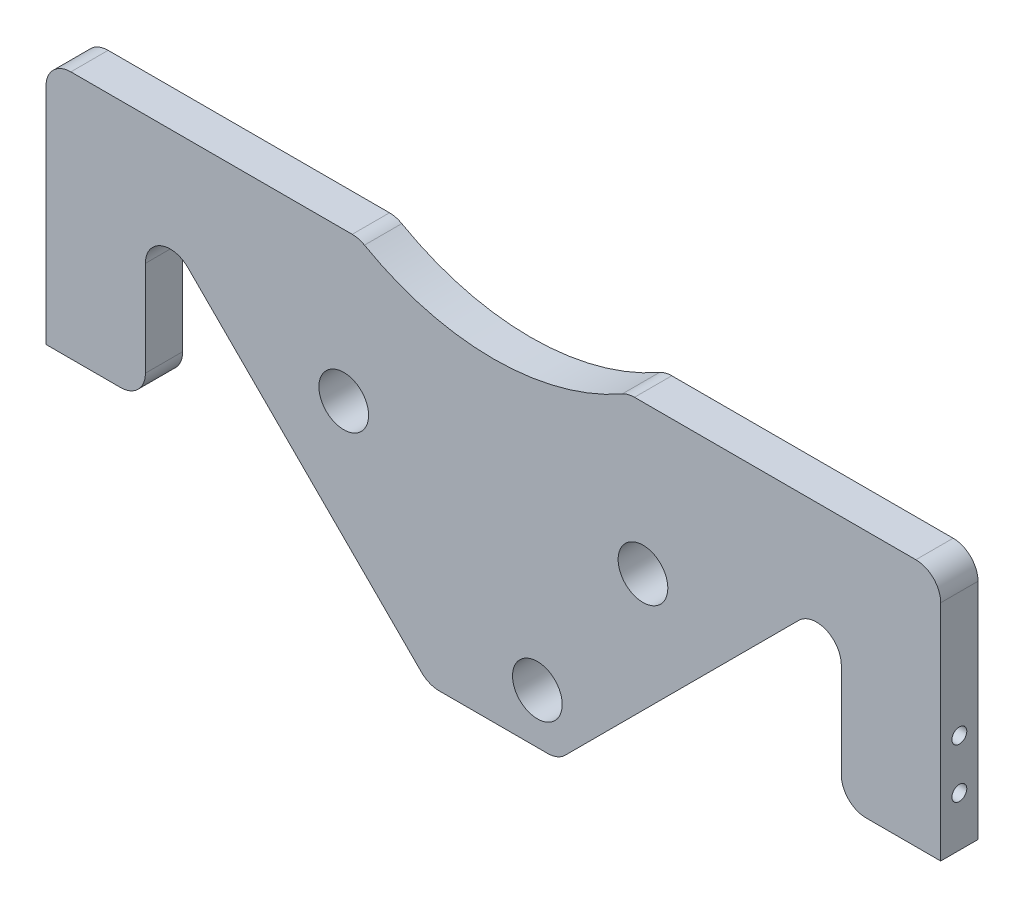
SolidWorks part; units mm, degrees
material "6061 Alloy"
ref_plane "Front Plane" through (0, 0, 0) normal (0, 0, 1) x (1, 0, 0)
ref_plane "Top Plane" through (0, 0, 0) normal (0, 1, 0) x (1, 0, 0)
ref_plane "Right Plane" through (0, 0, 0) normal (1, 0, 0) x (0, 0, -1)
sketch "LayoutSke"
sketch_block_instance "Gearing 2.0-1"
sketch_block "Gearing 2.0" parameters "D5"=76.2, "D6"=25.4, "D7"=101.6, "D8"=19.05, "D1"=228.6, "D2"=123.2, "D3"=85.227, "D4"=76.454, "D9"=39.0329, "D10"=76.454, "D11"=47.625, "D12"=63.5
sketch "Sketch2" plane through (0, 0, 0) normal (0, 0, 1) x (1, 0, 0)
  line L0 (-16.5, 33.2865) -> (16.5, 33.2865)
  line L1 (-114.3, 123.2) -> (114.3, 123.2)
  line L2 (-114.3, 123.2) -> (-114.3, 59.7)
  line L3 (-114.3, 59.7) -> (-42.9135, 59.7)
  line L4 (114.3, 123.2) -> (114.3, 59.7)
  line L5 (16.5, 33.2865) -> (42.9135, 59.7)
  line L6 (-16.5, 33.2865) -> (-42.9135, 59.7)
  line L7 (42.9135, 59.7) -> (114.3, 59.7)
  point P11 (0, 33.2865)
  dimension "D1" = 63.5
  dimension "D2" = 45
  dimension "D3" = 12.7
  dimension "D4" = 12.7
extrude "Boss-Extrude1" add sketch "Sketch2" along normal blind 9.525
hole_wizard "1/2 (0.5) Diameter Hole1" positions "Sketch3" profile "Sketch4" hole size "1/2" standard "ANSI Inch" end condition through all
sketch "Sketch3" plane through (0, 0, 9.525) normal (0, 0, 1) x (1, 0, 0)
  point P0 (-38.227, 85.227)
  point P3 (38.227, 85.227)
  point P6 (11.2395, 45.9865)
sketch "Sketch4" plane through (-38.227, 85.227, 9.525) normal (1, 0, 0) x (0, -1, 0)
  line L0 (0, 0) -> (0, 9.525)
  line L1 (0, 9.525) -> (6.35, 9.525)
  line L2 (6.35, 9.525) -> (6.35, 0)
  line L5 (6.35, 0) -> (0, 0)
  line L11 (0, -6.35) -> (0, 107.95) construction
  dimension "Thru Hole Dia." = 12.7
  dimension "Thru Hole Depth" = 9.525
ref_axis "MotorShaft" through (-48.0752, 23.3145, 0) along (0, 0, 1)
ref_axis "IntermediateShaft" through (11.2395, 45.9865, 0) along (0, 0, 1)
sketch "Sketch8" plane through (0, 0, 9.525) normal (0, 0, 1) x (1, 0, 0)
  line L0 (-114.3, 91.45) -> (114.3, 91.45) construction
  line L1 (-104.775, 113.675) -> (104.775, 113.675) construction
  line L2 (-104.775, 113.675) -> (-104.775, 69.225) construction
  line L3 (-104.775, 69.225) -> (104.775, 69.225) construction
  line L4 (104.775, 113.675) -> (104.775, 69.225) construction
  line L6 (-114.3, 123.2) -> (-114.3, 59.7) construction
  line L7 (114.3, 59.7) -> (114.3, 123.2) construction
  line L8 (114.3, 123.2) -> (-114.3, 123.2) construction
  point P4 (104.775, 91.45)
  point P7 (0, 69.225)
  dimension "D1" = 9.525
  dimension "D2" = 9.525
sketch "Sketch7" plane through (0, 0, 0) normal (0, 0, -1) x (-1, 0, 0)
  line L0 (-114.3, 123.2) -> (114.3, 123.2) construction
  line L1 (38.227, 85.227) -> (-38.227, 85.227) construction
  circle A0 centre (0, 180.35) radius 66.675
  point P4 (0, 123.2)
  point P6 (0, 113.675)
  dimension "D1" = 133.35
  dimension "D2" = 9.525
  dimension "D3" = 95.123
extrude "Cut-Extrude1" cut sketch "Sketch7" against normal through all
sketch "Sketch13" plane through (0, 0, 0) normal (0, 0, -1) x (-1, 0, 0)
  line L0 (42.9135, 59.7) -> (88.9, 105.6865)
  line L1 (88.9, 105.6865) -> (88.9, 59.7)
  line L3 (42.9135, 59.7) -> (88.9, 59.7)
  line L4 (114.3, 59.7) -> (42.9135, 59.7) construction
  line L5 (42.9135, 59.7) -> (16.5, 33.2865) construction
  line L6 (-42.9135, 59.7) -> (-88.9, 105.6865)
  line L7 (-88.9, 105.6865) -> (-88.9, 59.7)
  line L8 (-42.9135, 59.7) -> (-114.3, 59.7) construction
  line L9 (-88.9, 59.7) -> (-42.9135, 59.7)
  line L10 (-16.5, 33.2865) -> (-42.9135, 59.7) construction
  line L11 (-114.3, 59.7) -> (-114.3, 123.2) construction
  dimension "D1" = 25.4
extrude "Cut-Extrude2" cut sketch "Sketch13" against normal through all
fillet "Fillet1" radius 6.35 10 edges at (-114.3, 123.2, 4.7625) (114.3, 123.2, 4.7625) (34.3429, 123.2, 4.7625) (-34.3429, 123.2, 4.7625) (16.5, 33.2865, 4.7625) (-16.5, 33.2865, 4.7625) (-88.9, 105.6865, 4.7625) (-88.9, 59.7, 4.7625) (88.9, 105.6865, 4.7625) (88.9, 59.7, 4.7625)
hole_wizard "#10-24 Tapped Hole1" positions "Sketch11" profile "Sketch12" tap size "#10-24" standard "ANSI Inch"
sketch "Sketch11" plane through (-114.3, 0, 0) normal (-1, 0, 0) x (0, 0, 1)
  line L0 (4.7625, 123.2) -> (4.7625, 85.1) construction
  line L1 (0, 123.2) -> (9.525, 123.2) construction
  line L2 (4.7625, 85.1) -> (4.7625, 72.4) construction
  point P0 (4.7625, 85.1)
  point P2 (4.7625, 72.4)
  dimension "D1" = 12.7
  dimension "D2" = 38.1
sketch "Sketch12" plane through (-114.3, 85.1, 4.7625) normal (0, 1, 0) x (0, 0, 1)
  line L0 (0, 0) -> (0, 16.0887)
  line L1 (0, 16.0887) -> (1.8986, 14.9479)
  line L2 (1.8986, 14.9479) -> (1.8986, 0)
  line L5 (1.8986, 0) -> (0, 0)
  line L10 (0, 16.0887) -> (-1.8987, 14.9479) construction
  line L11 (0, -6.35) -> (0, 107.95) construction
  dimension "Tap Drill Dia." = 3.7973
  dimension "Tap Drill Depth" = 14.9479
  dimension "Drill Angle" = 118
cosmetic thread "Hole Thread1" parameters "D1"=9.652, "D2"=4.826
cosmetic thread "Hole Thread2" parameters "D1"=9.652, "D2"=4.826
mirror "Mirror1" about plane through (0, 0, 0) normal (1, 0, 0) of "#10-24 Tapped Hole1"
